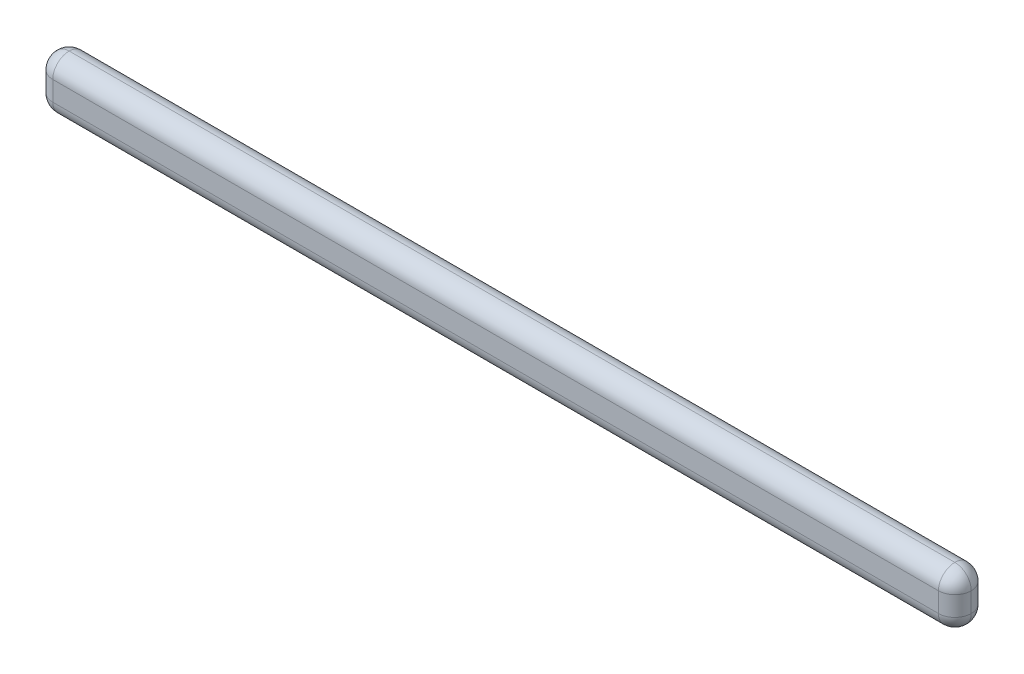
SolidWorks part; units mm, degrees
ref_plane "前基準面" through (0, 0, 0) normal (0, 0, 1) x (1, 0, 0)
ref_plane "上基準面" through (0, 0, 0) normal (0, 1, 0) x (1, 0, 0)
ref_plane "右基準面" through (0, 0, 0) normal (1, 0, 0) x (0, 0, -1)
ref_plane "平面1"
sketch "草圖1" plane through (0, 0, 0) normal (0, 0, 1) x (1, 0, 0)
  line L0 (-350, 20) -> (350, 20)
  line L1 (350, 20) -> (350, -20)
  line L2 (350, -20) -> (-350, -20)
  line L3 (-350, -20) -> (-350, 20)
  dimension "D1" = 700
  dimension "D2" = 40
extrude "擠出1" add sketch "草圖1" along normal blind 12.5 and the other way blind 12.5
fillet "圓角1" radius 12.5 4 edges at (0, -20, -12.5) (0, -20, 12.5) (0, 20, -12.5) (0, 20, 12.5)
fillet "圓角2" radius 12.5 12 edges at (-350, 16.3388, -8.8388) (-350, -16.3388, 8.8388) (-350, -16.3388, -8.8388) (350, -16.3388, 8.8388) (350, -16.3388, -8.8388) (350, 16.3388, -8.8388) (350, 16.3388, 8.8388) (-350, 0, 12.5) (-350, 16.3388, 8.8388) (-350, 0, -12.5) (350, 0, -12.5) (350, 0, 12.5)
